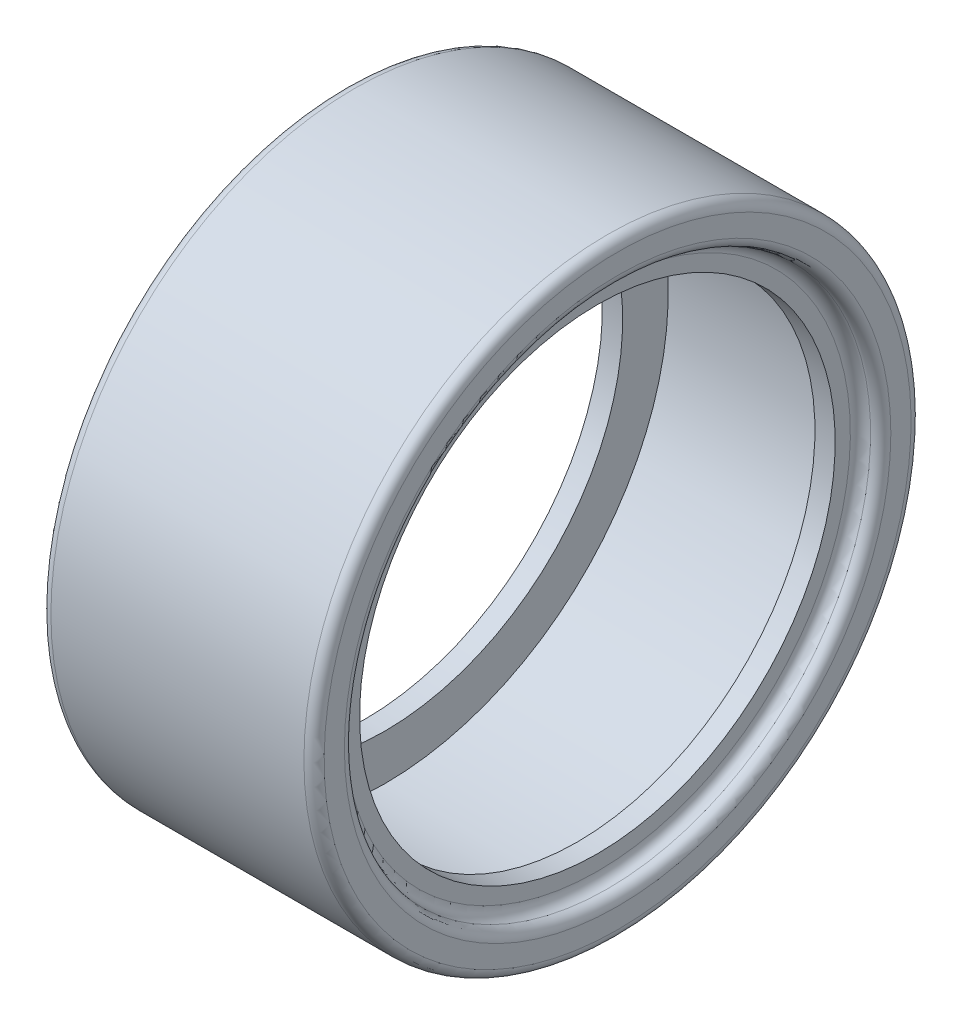
SolidWorks part; units mm, degrees
ref_plane "Front Plane" through (0, 0, 0) normal (0, 0, 1) x (1, 0, 0)
ref_plane "Top Plane" through (0, 0, 0) normal (0, 1, 0) x (1, 0, 0)
ref_plane "Right Plane" through (0, 0, 0) normal (1, 0, 0) x (0, 0, -1)
sketch "Sketch1" plane through (0, 0, 0) normal (0, 0, 1) x (1, 0, 0)
  line L0 (-11.5, 0) -> (11.5, 0) construction
  line L1 (-11.5, 23.5) -> (11.5, 23.5) construction
  line L2 (-11.5, 23.5) -> (-11.5, 26)
  line L3 (-11.5, 26) -> (-13.5, 26)
  line L4 (-13.5, 26) -> (-13.5, 30)
  line L5 (-13.5, 30) -> (13.5, 30)
  line L6 (13.5, 30) -> (13.5, 26)
  line L7 (13.5, 26) -> (11.5, 26)
  line L8 (11.5, 26) -> (11.5, 23.5)
  line L9 (-11.5, 23.5) -> (11.5, 23.5)
  point P4 (0, 0)
  dimension "D1" = 23
  dimension "D3" = 27
  dimension "D4" = 2.5
  dimension "D5" = 4
  dimension "D2" = 23.5
revolve "Revolve1" add sketch "Sketch1" angle 360 about L0
shell "Shell1" thickness 2 removed face at (11.5, -23.5, 0)
fillet "Fillet1" radius 1 6 edges at (11.5, -26, 0) (13.5, -26, 0) (-11.5, -26, 0) (-13.5, -26, 0) (-13.5, -30, 0) (13.5, -30, 0)
